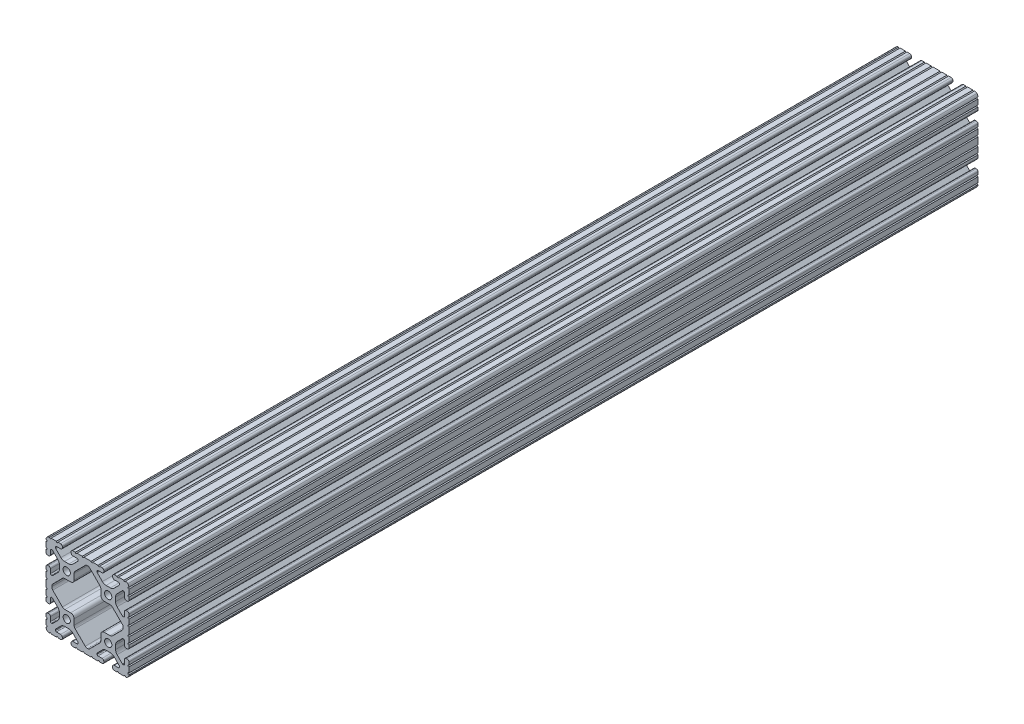
SolidWorks part; units mm, degrees
ref_plane "Front Plane" through (0, 0, 0) normal (0, 0, 1) x (1, 0, 0)
ref_plane "Top Plane" through (0, 0, 0) normal (0, 1, 0) x (1, 0, 0)
ref_plane "Right Plane" through (0, 0, 0) normal (1, 0, 0) x (0, 0, -1)
sketch "Sketch1" plane through (0, 0, 0) normal (0, 0, 1) x (1, 0, 0)
  line L0 (0, 38.1) -> (0, -38.1) construction
  line L1 (-38.1, -38.1) -> (38.1, -38.1) construction
  line L2 (-38.1, -38.1) -> (-38.1, 38.1) construction
  line L3 (-38.1, 38.1) -> (38.1, 38.1) construction
  line L4 (38.1, -38.1) -> (38.1, 38.1) construction
  line L5 (0, 38.1) -> (0, -38.1) construction
  line L6 (-38.1, 0) -> (38.1, 0) construction
  line L7 (-19.05, 19.05) -> (19.05, 19.05) construction
  line L8 (-19.05, 19.05) -> (-19.05, -19.05) construction
  line L9 (-19.05, -19.05) -> (19.05, -19.05) construction
  line L10 (19.05, 19.05) -> (19.05, -19.05) construction
  line L11 (-23.114, 38.1) -> (-23.114, -38.1) construction
  line L12 (-23.114, -38.1) -> (-14.986, 38.1) construction
  line L13 (-14.986, 38.1) -> (-14.986, -38.1) construction
  circle A0 centre (19.05, 19.05) radius 3.3274
  point P0 (0, 0)
  point P9 (0, 0)
  point P12 (-19.05, 0)
  line B0 (-11.3637, -22.8433) -> (-2.0515, -32.1555)
  line B1 (-12.2936, -15.4686) -> (-12.2936, -20.5983)
  line B2 (-20.769, -12.2936) -> (-15.4686, -12.2936)
  line B3 (-31.9021, -2.4756) -> (-23.0141, -11.3637)
  line B4 (-23.0141, 11.3637) -> (-31.9021, 2.4756)
  line B5 (-15.4686, 12.2936) -> (-20.769, 12.2936)
  line B6 (-12.2936, 20.5983) -> (-12.2936, 15.4686)
  line B7 (-2.0515, 32.1555) -> (-11.3637, 22.8433)
  line B8 (11.3637, 22.8433) -> (2.0515, 32.1555)
  line B9 (12.2936, 15.4686) -> (12.2936, 20.5983)
  line B10 (20.769, 12.2936) -> (15.4686, 12.2936)
  line B11 (31.9021, 2.4756) -> (23.0141, 11.3637)
  line B12 (23.0141, -11.3637) -> (31.9021, -2.4756)
  line B13 (15.4686, -12.2936) -> (20.769, -12.2936)
  line B14 (12.2936, -20.5983) -> (12.2936, -15.4686)
  line B15 (2.0515, -32.1555) -> (11.3637, -22.8433)
  line B16 (-4.7773, 38.1) -> (-9.6053, 38.1)
  line B17 (-11.1289, 38.1) -> (-13.4112, 38.1)
  line B18 (-14.986, 36.5252) -> (-14.986, 35.6108)
  line B19 (-13.4112, 34.036) -> (-9.652, 34.036)
  line B20 (-8.763, 33.147) -> (-8.763, 32.4935)
  line B21 (-9.0234, 31.8649) -> (-13.6907, 27.1976)
  line B22 (-17.0493, 25.8064) -> (-21.0507, 25.8064)
  line B23 (-24.4093, 27.1976) -> (-29.1002, 31.8885)
  line B24 (-29.337, 32.7207) -> (-29.337, 33.147)
  line B25 (-28.448, 34.036) -> (-24.6888, 34.036)
  line B26 (-23.114, 35.6108) -> (-23.114, 36.5252)
  line B27 (-24.6888, 38.1) -> (-27.0772, 38.1)
  line B28 (-28.6011, 38.1) -> (-33.4288, 38.1)
  line B29 (-38.1, 33.373) -> (-38.1, 28.5453)
  line B30 (-38.1, 27.0238) -> (-38.1, 24.6302)
  line B31 (-36.5252, 23.0554) -> (-35.6108, 23.0554)
  line B32 (-34.036, 24.6302) -> (-34.036, 28.448)
  line B33 (-33.147, 29.337) -> (-32.6643, 29.337)
  line B34 (-32.0357, 29.0766) -> (-27.1976, 24.2385)
  line B35 (-25.8064, 20.8799) -> (-25.8064, 17.2201)
  line B36 (-27.1976, 13.8615) -> (-31.9489, 9.1101)
  line B37 (-32.7869, 8.763) -> (-33.0603, 8.763)
  line B38 (-34.036, 9.7387) -> (-34.036, 13.4698)
  line B39 (-35.6108, 15.0446) -> (-36.5252, 15.0446)
  line B40 (-38.1, 13.4698) -> (-38.1, 11.075)
  line B41 (-38.1, 9.552) -> (-38.1, 4.7238)
  line B42 (-38.1, 3.2007) -> (-38.1, -3.2007)
  line B43 (-38.1, -4.7238) -> (-38.1, -9.552)
  line B44 (-38.1, -11.075) -> (-38.1, -13.4698)
  line B45 (-36.5252, -15.0446) -> (-35.6108, -15.0446)
  line B46 (-34.036, -13.4698) -> (-34.036, -9.7387)
  line B47 (-33.0603, -8.763) -> (-32.7869, -8.763)
  line B48 (-31.9489, -9.1101) -> (-27.1976, -13.8615)
  line B49 (-25.8064, -17.2201) -> (-25.8064, -20.8799)
  line B50 (-27.1976, -24.2385) -> (-32.0357, -29.0766)
  line B51 (-32.6643, -29.337) -> (-33.147, -29.337)
  line B52 (-34.036, -28.448) -> (-34.036, -24.6302)
  line B53 (-35.6108, -23.0554) -> (-36.5252, -23.0554)
  line B54 (-38.1, -24.6302) -> (-38.1, -27.0238)
  line B55 (-38.1, -28.5453) -> (-38.1, -33.373)
  line B56 (-33.4288, -38.1) -> (-28.6011, -38.1)
  line B57 (-27.0772, -38.1) -> (-24.6888, -38.1)
  line B58 (-23.114, -36.5252) -> (-23.114, -35.6108)
  line B59 (-24.6888, -34.036) -> (-28.448, -34.036)
  line B60 (-29.337, -33.147) -> (-29.337, -32.7207)
  line B61 (-29.1002, -31.8885) -> (-24.4093, -27.1976)
  line B62 (-21.0507, -25.8064) -> (-17.0493, -25.8064)
  line B63 (-13.6907, -27.1976) -> (-9.0234, -31.8649)
  line B64 (-8.763, -32.4935) -> (-8.763, -33.147)
  line B65 (-9.652, -34.036) -> (-13.4112, -34.036)
  line B66 (-14.986, -35.6108) -> (-14.986, -36.5252)
  line B67 (-13.4112, -38.1) -> (-11.1289, -38.1)
  line B68 (-9.6053, -38.1) -> (-4.7773, -38.1)
  line B69 (-3.2537, -38.1) -> (3.2537, -38.1)
  line B70 (4.7773, -38.1) -> (9.6053, -38.1)
  line B71 (11.1289, -38.1) -> (13.4112, -38.1)
  line B72 (14.986, -36.5252) -> (14.986, -35.6108)
  line B73 (13.4112, -34.036) -> (9.652, -34.036)
  line B74 (8.763, -33.147) -> (8.763, -32.4935)
  line B75 (9.0234, -31.8649) -> (13.6907, -27.1976)
  line B76 (17.0493, -25.8064) -> (21.0507, -25.8064)
  line B77 (24.4093, -27.1976) -> (29.1002, -31.8885)
  line B78 (29.337, -32.7207) -> (29.337, -33.147)
  line B79 (28.448, -34.036) -> (24.6888, -34.036)
  line B80 (23.114, -35.6108) -> (23.114, -36.5252)
  line B81 (24.6888, -38.1) -> (27.0772, -38.1)
  line B82 (28.6011, -38.1) -> (33.4288, -38.1)
  line B83 (38.1, -33.373) -> (38.1, -28.5453)
  line B84 (38.1, -27.0238) -> (38.1, -24.6302)
  line B85 (36.5252, -23.0554) -> (35.6108, -23.0554)
  line B86 (34.036, -24.6302) -> (34.036, -28.448)
  line B87 (33.147, -29.337) -> (32.6643, -29.337)
  line B88 (32.0357, -29.0766) -> (27.1976, -24.2385)
  line B89 (25.8064, -20.8799) -> (25.8064, -17.2201)
  line B90 (27.1976, -13.8615) -> (31.9489, -9.1101)
  line B91 (32.7869, -8.763) -> (33.0603, -8.763)
  line B92 (34.036, -9.7387) -> (34.036, -13.4698)
  line B93 (35.6108, -15.0446) -> (36.5252, -15.0446)
  line B94 (38.1, -13.4698) -> (38.1, -11.075)
  line B95 (38.1, -9.552) -> (38.1, -4.7238)
  line B96 (38.1, -3.2007) -> (38.1, 3.2007)
  line B97 (38.1, 4.7238) -> (38.1, 9.552)
  line B98 (38.1, 11.075) -> (38.1, 13.4698)
  line B99 (36.5252, 15.0446) -> (35.6108, 15.0446)
  line B100 (34.036, 13.4698) -> (34.036, 9.7387)
  line B101 (33.0603, 8.763) -> (32.7869, 8.763)
  line B102 (31.9489, 9.1101) -> (27.1976, 13.8615)
  line B103 (25.8064, 17.2201) -> (25.8064, 20.8799)
  line B104 (27.1976, 24.2385) -> (32.0357, 29.0766)
  line B105 (32.6643, 29.337) -> (33.147, 29.337)
  line B106 (34.036, 28.448) -> (34.036, 24.6302)
  line B107 (35.6108, 23.0554) -> (36.5252, 23.0554)
  line B108 (38.1, 24.6302) -> (38.1, 27.0238)
  line B109 (38.1, 28.5453) -> (38.1, 33.373)
  line B110 (33.4288, 38.1) -> (28.6011, 38.1)
  line B111 (27.0772, 38.1) -> (24.6888, 38.1)
  line B112 (23.114, 36.5252) -> (23.114, 35.6108)
  line B113 (24.6888, 34.036) -> (28.448, 34.036)
  line B114 (29.337, 33.147) -> (29.337, 32.7207)
  line B115 (29.1002, 31.8885) -> (24.4093, 27.1976)
  line B116 (21.0507, 25.8064) -> (17.0493, 25.8064)
  line B117 (13.6907, 27.1976) -> (9.0234, 31.8649)
  line B118 (8.763, 32.4935) -> (8.763, 33.147)
  line B119 (9.652, 34.036) -> (13.4112, 34.036)
  line B120 (14.986, 35.6108) -> (14.986, 36.5252)
  line B121 (13.4112, 38.1) -> (11.1289, 38.1)
  line B122 (9.6053, 38.1) -> (4.7773, 38.1)
  line B123 (3.2537, 38.1) -> (-3.2537, 38.1)
  circle B124 centre (-19.05, 19.05) radius 3.3274
  circle B125 centre (-19.05, -19.05) radius 3.3274
  circle B126 centre (19.05, -19.05) radius 3.3274
  circle B127 centre (19.05, 19.05) radius 3.3274
  arc B128 (0, -33.011) -> (2.0515, -32.1555) centre (-0.0139, -30.09) ccw
  arc B129 (-2.0515, -32.1555) -> (0, -33.011) centre (0.0139, -30.09) ccw
  arc B130 (-12.2936, -20.5983) -> (-11.3637, -22.8433) centre (-9.1186, -20.5983) ccw
  arc B131 (-12.2936, -15.4686) -> (-15.4686, -12.2936) centre (-15.4686, -15.4686) ccw
  arc B132 (-23.0141, -11.3637) -> (-20.769, -12.2936) centre (-20.769, -9.1186) ccw
  arc B133 (-32.7287, 0) -> (-31.9021, -2.4756) centre (-29.8367, -0.4102) ccw
  arc B134 (-31.9021, 2.4756) -> (-32.7287, 0) centre (-29.8367, 0.4102) ccw
  arc B135 (-20.769, 12.2936) -> (-23.0141, 11.3637) centre (-20.769, 9.1186) ccw
  arc B136 (-15.4686, 12.2936) -> (-12.2936, 15.4686) centre (-15.4686, 15.4686) ccw
  arc B137 (-11.3637, 22.8433) -> (-12.2936, 20.5983) centre (-9.1186, 20.5983) ccw
  arc B138 (0, 33.011) -> (-2.0515, 32.1555) centre (0.0139, 30.09) ccw
  arc B139 (2.0515, 32.1555) -> (0, 33.011) centre (-0.0139, 30.09) ccw
  arc B140 (12.2936, 20.5983) -> (11.3637, 22.8433) centre (9.1186, 20.5983) ccw
  arc B141 (12.2936, 15.4686) -> (15.4686, 12.2936) centre (15.4686, 15.4686) ccw
  arc B142 (23.0141, 11.3637) -> (20.769, 12.2936) centre (20.769, 9.1186) ccw
  arc B143 (32.7287, 0) -> (31.9021, 2.4756) centre (29.8367, 0.4102) ccw
  arc B144 (31.9021, -2.4756) -> (32.7287, 0) centre (29.8367, -0.4102) ccw
  arc B145 (20.769, -12.2936) -> (23.0141, -11.3637) centre (20.769, -9.1186) ccw
  arc B146 (15.4686, -12.2936) -> (12.2936, -15.4686) centre (15.4686, -15.4686) ccw
  arc B147 (11.3637, -22.8433) -> (12.2936, -20.5983) centre (9.1186, -20.5983) ccw
  arc B148 (-4.7773, 38.1) -> (-3.2537, 38.1) centre (-4.0155, 38.0824) ccw
  arc B149 (-11.1289, 38.1) -> (-9.6053, 38.1) centre (-10.3671, 38.0824) ccw
  arc B150 (-13.4112, 38.1) -> (-14.986, 36.5252) centre (-13.4112, 36.5252) ccw
  arc B151 (-14.986, 35.6108) -> (-13.4112, 34.036) centre (-13.4112, 35.6108) ccw
  arc B152 (-8.763, 33.147) -> (-9.652, 34.036) centre (-9.652, 33.147) ccw
  arc B153 (-9.0234, 31.8649) -> (-8.763, 32.4935) centre (-9.652, 32.4935) ccw
  arc B154 (-17.0493, 25.8064) -> (-13.6907, 27.1976) centre (-17.0493, 30.5562) ccw
  arc B155 (-24.4093, 27.1976) -> (-21.0507, 25.8064) centre (-21.0507, 30.5562) ccw
  arc B156 (-29.337, 32.7207) -> (-29.1002, 31.8885) centre (-28.4716, 32.5172) ccw
  arc B157 (-28.448, 34.036) -> (-29.337, 33.147) centre (-28.448, 33.147) ccw
  arc B158 (-24.6888, 34.036) -> (-23.114, 35.6108) centre (-24.6888, 35.6108) ccw
  arc B159 (-23.114, 36.5252) -> (-24.6888, 38.1) centre (-24.6888, 36.5252) ccw
  arc B160 (-28.6011, 38.1) -> (-27.0772, 38.1) centre (-27.8392, 38.0824) ccw
  arc B161 (-34.9527, 38.1) -> (-33.4288, 38.1) centre (-34.1907, 38.0824) ccw
  arc B162 (-34.9527, 38.1) -> (-37.0861, 37.1826) centre (-34.8521, 34.9266) ccw
  arc B163 (-37.0861, 37.1826) -> (-38.1, 34.8455) centre (-34.925, 34.8566) ccw
  arc B164 (-38.1, 33.373) -> (-38.1, 34.8455) centre (-37.9035, 34.1092) ccw
  arc B165 (-38.1, 27.0238) -> (-38.1, 28.5453) centre (-37.9035, 27.7845) ccw
  arc B166 (-38.1, 24.6302) -> (-36.5252, 23.0554) centre (-36.5252, 24.6302) ccw
  arc B167 (-35.6108, 23.0554) -> (-34.036, 24.6302) centre (-35.6108, 24.6302) ccw
  arc B168 (-33.147, 29.337) -> (-34.036, 28.448) centre (-33.147, 28.448) ccw
  arc B169 (-32.0357, 29.0766) -> (-32.6643, 29.337) centre (-32.6643, 28.448) ccw
  arc B170 (-25.8064, 20.8799) -> (-27.1976, 24.2385) centre (-30.5562, 20.8799) ccw
  arc B171 (-27.1976, 13.8615) -> (-25.8064, 17.2201) centre (-30.5562, 17.2201) ccw
  arc B172 (-32.7869, 8.763) -> (-31.9489, 9.1101) centre (-32.7869, 9.9481) ccw
  arc B173 (-34.036, 9.7387) -> (-33.0603, 8.763) centre (-33.0603, 9.7387) ccw
  arc B174 (-34.036, 13.4698) -> (-35.6108, 15.0446) centre (-35.6108, 13.4698) ccw
  arc B175 (-36.5252, 15.0446) -> (-38.1, 13.4698) centre (-36.5252, 13.4698) ccw
  arc B176 (-38.1, 9.552) -> (-38.1, 11.075) centre (-37.9035, 10.3135) ccw
  arc B177 (-38.1, 3.2007) -> (-38.1, 4.7238) centre (-37.9035, 3.9622) ccw
  arc B178 (-38.1, -4.7238) -> (-38.1, -3.2007) centre (-37.9035, -3.9622) ccw
  arc B179 (-38.1, -11.075) -> (-38.1, -9.552) centre (-37.9035, -10.3135) ccw
  arc B180 (-38.1, -13.4698) -> (-36.5252, -15.0446) centre (-36.5252, -13.4698) ccw
  arc B181 (-35.6108, -15.0446) -> (-34.036, -13.4698) centre (-35.6108, -13.4698) ccw
  arc B182 (-33.0603, -8.763) -> (-34.036, -9.7387) centre (-33.0603, -9.7387) ccw
  arc B183 (-31.9489, -9.1101) -> (-32.7869, -8.763) centre (-32.7869, -9.9481) ccw
  arc B184 (-25.8064, -17.2201) -> (-27.1976, -13.8615) centre (-30.5562, -17.2201) ccw
  arc B185 (-27.1976, -24.2385) -> (-25.8064, -20.8799) centre (-30.5562, -20.8799) ccw
  arc B186 (-32.6643, -29.337) -> (-32.0357, -29.0766) centre (-32.6643, -28.448) ccw
  arc B187 (-34.036, -28.448) -> (-33.147, -29.337) centre (-33.147, -28.448) ccw
  arc B188 (-34.036, -24.6302) -> (-35.6108, -23.0554) centre (-35.6108, -24.6302) ccw
  arc B189 (-36.5252, -23.0554) -> (-38.1, -24.6302) centre (-36.5252, -24.6302) ccw
  arc B190 (-38.1, -28.5453) -> (-38.1, -27.0238) centre (-37.9035, -27.7845) ccw
  arc B191 (-38.1, -34.8455) -> (-38.1, -33.373) centre (-37.9035, -34.1092) ccw
  arc B192 (-38.1, -34.8455) -> (-37.0861, -37.1826) centre (-34.925, -34.8566) ccw
  arc B193 (-37.0861, -37.1826) -> (-34.9527, -38.1) centre (-34.8521, -34.9266) ccw
  arc B194 (-33.4288, -38.1) -> (-34.9527, -38.1) centre (-34.1907, -38.0824) ccw
  arc B195 (-27.0772, -38.1) -> (-28.6011, -38.1) centre (-27.8392, -38.0824) ccw
  arc B196 (-24.6888, -38.1) -> (-23.114, -36.5252) centre (-24.6888, -36.5252) ccw
  arc B197 (-23.114, -35.6108) -> (-24.6888, -34.036) centre (-24.6888, -35.6108) ccw
  arc B198 (-29.337, -33.147) -> (-28.448, -34.036) centre (-28.448, -33.147) ccw
  arc B199 (-29.1002, -31.8885) -> (-29.337, -32.7207) centre (-28.4716, -32.5172) ccw
  arc B200 (-21.0507, -25.8064) -> (-24.4093, -27.1976) centre (-21.0507, -30.5562) ccw
  arc B201 (-13.6907, -27.1976) -> (-17.0493, -25.8064) centre (-17.0493, -30.5562) ccw
  arc B202 (-8.763, -32.4935) -> (-9.0234, -31.8649) centre (-9.652, -32.4935) ccw
  arc B203 (-9.652, -34.036) -> (-8.763, -33.147) centre (-9.652, -33.147) ccw
  arc B204 (-13.4112, -34.036) -> (-14.986, -35.6108) centre (-13.4112, -35.6108) ccw
  arc B205 (-14.986, -36.5252) -> (-13.4112, -38.1) centre (-13.4112, -36.5252) ccw
  arc B206 (-9.6053, -38.1) -> (-11.1289, -38.1) centre (-10.3671, -38.0824) ccw
  arc B207 (-3.2537, -38.1) -> (-4.7773, -38.1) centre (-4.0155, -38.0824) ccw
  arc B208 (4.7773, -38.1) -> (3.2537, -38.1) centre (4.0155, -38.0824) ccw
  arc B209 (11.1289, -38.1) -> (9.6053, -38.1) centre (10.3671, -38.0824) ccw
  arc B210 (13.4112, -38.1) -> (14.986, -36.5252) centre (13.4112, -36.5252) ccw
  arc B211 (14.986, -35.6108) -> (13.4112, -34.036) centre (13.4112, -35.6108) ccw
  arc B212 (8.763, -33.147) -> (9.652, -34.036) centre (9.652, -33.147) ccw
  arc B213 (9.0234, -31.8649) -> (8.763, -32.4935) centre (9.652, -32.4935) ccw
  arc B214 (17.0493, -25.8064) -> (13.6907, -27.1976) centre (17.0493, -30.5562) ccw
  arc B215 (24.4093, -27.1976) -> (21.0507, -25.8064) centre (21.0507, -30.5562) ccw
  arc B216 (29.337, -32.7207) -> (29.1002, -31.8885) centre (28.4716, -32.5172) ccw
  arc B217 (28.448, -34.036) -> (29.337, -33.147) centre (28.448, -33.147) ccw
  arc B218 (24.6888, -34.036) -> (23.114, -35.6108) centre (24.6888, -35.6108) ccw
  arc B219 (23.114, -36.5252) -> (24.6888, -38.1) centre (24.6888, -36.5252) ccw
  arc B220 (28.6011, -38.1) -> (27.0772, -38.1) centre (27.8392, -38.0824) ccw
  arc B221 (34.9527, -38.1) -> (33.4288, -38.1) centre (34.1907, -38.0824) ccw
  arc B222 (34.9527, -38.1) -> (37.0861, -37.1826) centre (34.8521, -34.9266) ccw
  arc B223 (37.0861, -37.1826) -> (38.1, -34.8455) centre (34.925, -34.8566) ccw
  arc B224 (38.1, -33.373) -> (38.1, -34.8455) centre (37.9035, -34.1092) ccw
  arc B225 (38.1, -27.0238) -> (38.1, -28.5453) centre (37.9035, -27.7845) ccw
  arc B226 (38.1, -24.6302) -> (36.5252, -23.0554) centre (36.5252, -24.6302) ccw
  arc B227 (35.6108, -23.0554) -> (34.036, -24.6302) centre (35.6108, -24.6302) ccw
  arc B228 (33.147, -29.337) -> (34.036, -28.448) centre (33.147, -28.448) ccw
  arc B229 (32.0357, -29.0766) -> (32.6643, -29.337) centre (32.6643, -28.448) ccw
  arc B230 (25.8064, -20.8799) -> (27.1976, -24.2385) centre (30.5562, -20.8799) ccw
  arc B231 (27.1976, -13.8615) -> (25.8064, -17.2201) centre (30.5562, -17.2201) ccw
  arc B232 (32.7869, -8.763) -> (31.9489, -9.1101) centre (32.7869, -9.9481) ccw
  arc B233 (34.036, -9.7387) -> (33.0603, -8.763) centre (33.0603, -9.7387) ccw
  arc B234 (34.036, -13.4698) -> (35.6108, -15.0446) centre (35.6108, -13.4698) ccw
  arc B235 (36.5252, -15.0446) -> (38.1, -13.4698) centre (36.5252, -13.4698) ccw
  arc B236 (38.1, -9.552) -> (38.1, -11.075) centre (37.9035, -10.3135) ccw
  arc B237 (38.1, -3.2007) -> (38.1, -4.7238) centre (37.9035, -3.9622) ccw
  arc B238 (38.1, 4.7238) -> (38.1, 3.2007) centre (37.9035, 3.9622) ccw
  arc B239 (38.1, 11.075) -> (38.1, 9.552) centre (37.9035, 10.3135) ccw
  arc B240 (38.1, 13.4698) -> (36.5252, 15.0446) centre (36.5252, 13.4698) ccw
  arc B241 (35.6108, 15.0446) -> (34.036, 13.4698) centre (35.6108, 13.4698) ccw
  arc B242 (33.0603, 8.763) -> (34.036, 9.7387) centre (33.0603, 9.7387) ccw
  arc B243 (31.9489, 9.1101) -> (32.7869, 8.763) centre (32.7869, 9.9481) ccw
  arc B244 (25.8064, 17.2201) -> (27.1976, 13.8615) centre (30.5562, 17.2201) ccw
  arc B245 (27.1976, 24.2385) -> (25.8064, 20.8799) centre (30.5562, 20.8799) ccw
  arc B246 (32.6643, 29.337) -> (32.0357, 29.0766) centre (32.6643, 28.448) ccw
  arc B247 (34.036, 28.448) -> (33.147, 29.337) centre (33.147, 28.448) ccw
  arc B248 (34.036, 24.6302) -> (35.6108, 23.0554) centre (35.6108, 24.6302) ccw
  arc B249 (36.5252, 23.0554) -> (38.1, 24.6302) centre (36.5252, 24.6302) ccw
  arc B250 (38.1, 28.5453) -> (38.1, 27.0238) centre (37.9035, 27.7845) ccw
  arc B251 (38.1, 34.8455) -> (38.1, 33.373) centre (37.9035, 34.1092) ccw
  arc B252 (38.1, 34.8455) -> (37.0861, 37.1826) centre (34.925, 34.8566) ccw
  arc B253 (37.0861, 37.1826) -> (34.9527, 38.1) centre (34.8521, 34.9266) ccw
  arc B254 (33.4288, 38.1) -> (34.9527, 38.1) centre (34.1907, 38.0824) ccw
  arc B255 (27.0772, 38.1) -> (28.6011, 38.1) centre (27.8392, 38.0824) ccw
  arc B256 (24.6888, 38.1) -> (23.114, 36.5252) centre (24.6888, 36.5252) ccw
  arc B257 (23.114, 35.6108) -> (24.6888, 34.036) centre (24.6888, 35.6108) ccw
  arc B258 (29.337, 33.147) -> (28.448, 34.036) centre (28.448, 33.147) ccw
  arc B259 (29.1002, 31.8885) -> (29.337, 32.7207) centre (28.4716, 32.5172) ccw
  arc B260 (21.0507, 25.8064) -> (24.4093, 27.1976) centre (21.0507, 30.5562) ccw
  arc B261 (13.6907, 27.1976) -> (17.0493, 25.8064) centre (17.0493, 30.5562) ccw
  arc B262 (8.763, 32.4935) -> (9.0234, 31.8649) centre (9.652, 32.4935) ccw
  arc B263 (9.652, 34.036) -> (8.763, 33.147) centre (9.652, 33.147) ccw
  arc B264 (13.4112, 34.036) -> (14.986, 35.6108) centre (13.4112, 35.6108) ccw
  arc B265 (14.986, 36.5252) -> (13.4112, 38.1) centre (13.4112, 36.5252) ccw
  arc B266 (9.6053, 38.1) -> (11.1289, 38.1) centre (10.3671, 38.0824) ccw
  arc B267 (3.2537, 38.1) -> (4.7773, 38.1) centre (4.0155, 38.0824) ccw
  dimension "Center Hole Diameter" = 6.6548
  dimension "Rail Width" = 76.2
  dimension "Rail Height" = 76.2
  dimension "T-Slot Width" = 8.128
sketch_block_instance "Block1-1"
sketch_block "Block1"
sketch "Sketch2" plane through (0, 0, 0) normal (1, 0, 0) x (0, 0, -1)
  line L0 (-390, 0) -> (390, 0) construction
  line L1 (-390, 38.1) -> (-390, -38.1) construction
  line L2 (-390, -38.1) -> (390, -38.1) construction
  line L3 (390, -38.1) -> (390, 38.1) construction
  line L4 (-288.4, 0) -> (-288.4, 38.1) construction
  line L5 (-288.4, 38.1) -> (288.4, 38.1) construction
  line L6 (288.4, 38.1) -> (288.4, 0) construction
  point P5 (288.4, 0)
  point P10 (-288.4, 0)
  dimension "D1" = 101.6
  dimension "Length" = 780
  dimension "D2" = 101.6
sketch "Sketch3" plane through (0, 0, 0) normal (0, 0, 1) x (1, 0, 0)
  line L0 (-11.3637, -22.8433) -> (-2.0515, -32.1555) construction
  line L1 (-12.2936, -15.4686) -> (-12.2936, -20.5983) construction
  line L2 (-20.769, -12.2936) -> (-15.4686, -12.2936) construction
  line L3 (-31.9021, -2.4756) -> (-23.0141, -11.3637) construction
  line L4 (-23.0141, 11.3637) -> (-31.9021, 2.4756) construction
  line L5 (-15.4686, 12.2936) -> (-20.769, 12.2936) construction
  line L6 (-12.2936, 20.5983) -> (-12.2936, 15.4686) construction
  line L7 (-2.0515, 32.1555) -> (-11.3637, 22.8433) construction
  line L8 (11.3637, 22.8433) -> (2.0515, 32.1555) construction
  line L9 (12.2936, 15.4686) -> (12.2936, 20.5983) construction
  line L10 (20.769, 12.2936) -> (15.4686, 12.2936) construction
  line L11 (31.9021, 2.4756) -> (23.0141, 11.3637) construction
  line L12 (23.0141, -11.3637) -> (31.9021, -2.4756) construction
  line L13 (15.4686, -12.2936) -> (20.769, -12.2936) construction
  line L14 (12.2936, -20.5983) -> (12.2936, -15.4686) construction
  line L15 (2.0515, -32.1555) -> (11.3637, -22.8433) construction
  line L16 (34.036, 28.448) -> (34.036, 24.6302) construction
  line L17 (35.6108, 23.0554) -> (36.5252, 23.0554) construction
  line L18 (38.1, 24.6302) -> (38.1, 27.0238) construction
  line L19 (38.1, 28.5453) -> (38.1, 33.373) construction
  line L20 (33.4288, 38.1) -> (28.6011, 38.1) construction
  line L21 (27.0772, 38.1) -> (24.6888, 38.1) construction
  line L22 (23.114, 36.5252) -> (23.114, 35.6108) construction
  line L23 (24.6888, 34.036) -> (28.448, 34.036) construction
  line L24 (29.337, 33.147) -> (29.337, 32.7207) construction
  line L25 (29.1002, 31.8885) -> (24.4093, 27.1976) construction
  line L26 (21.0507, 25.8064) -> (17.0493, 25.8064) construction
  line L27 (13.6907, 27.1976) -> (9.0234, 31.8649) construction
  line L28 (8.763, 32.4935) -> (8.763, 33.147) construction
  line L29 (9.652, 34.036) -> (13.4112, 34.036) construction
  line L30 (14.986, 35.6108) -> (14.986, 36.5252) construction
  line L31 (13.4112, 38.1) -> (11.1289, 38.1) construction
  line L32 (9.6053, 38.1) -> (4.7773, 38.1) construction
  line L33 (3.2537, 38.1) -> (-3.2537, 38.1) construction
  line L34 (-4.7773, 38.1) -> (-9.6053, 38.1) construction
  line L35 (-11.1289, 38.1) -> (-13.4112, 38.1) construction
  line L36 (-14.986, 36.5252) -> (-14.986, 35.6108) construction
  line L37 (-13.4112, 34.036) -> (-9.652, 34.036) construction
  line L38 (-8.763, 33.147) -> (-8.763, 32.4935) construction
  line L39 (-9.0234, 31.8649) -> (-13.6907, 27.1976) construction
  line L40 (-17.0493, 25.8064) -> (-21.0507, 25.8064) construction
  line L41 (-24.4093, 27.1976) -> (-29.1002, 31.8885) construction
  line L42 (-29.337, 32.7207) -> (-29.337, 33.147) construction
  line L43 (-28.448, 34.036) -> (-24.6888, 34.036) construction
  line L44 (-23.114, 35.6108) -> (-23.114, 36.5252) construction
  line L45 (-24.6888, 38.1) -> (-27.0772, 38.1) construction
  line L46 (-28.6011, 38.1) -> (-33.4288, 38.1) construction
  line L47 (-38.1, 33.373) -> (-38.1, 28.5453) construction
  line L48 (-38.1, 27.0238) -> (-38.1, 24.6302) construction
  line L49 (-36.5252, 23.0554) -> (-35.6108, 23.0554) construction
  line L50 (-34.036, 24.6302) -> (-34.036, 28.448) construction
  line L51 (-33.147, 29.337) -> (-32.6643, 29.337) construction
  line L52 (-32.0357, 29.0766) -> (-27.1976, 24.2385) construction
  line L53 (-25.8064, 20.8799) -> (-25.8064, 17.2201) construction
  line L54 (-27.1976, 13.8615) -> (-31.9489, 9.1101) construction
  line L55 (-32.7869, 8.763) -> (-33.0603, 8.763) construction
  line L56 (-34.036, 9.7387) -> (-34.036, 13.4698) construction
  line L57 (-35.6108, 15.0446) -> (-36.5252, 15.0446) construction
  line L58 (-38.1, 13.4698) -> (-38.1, 11.075) construction
  line L59 (-38.1, 9.552) -> (-38.1, 4.7238) construction
  line L60 (-38.1, 3.2007) -> (-38.1, -3.2007) construction
  line L61 (-38.1, -4.7238) -> (-38.1, -9.552) construction
  line L62 (-38.1, -11.075) -> (-38.1, -13.4698) construction
  line L63 (-36.5252, -15.0446) -> (-35.6108, -15.0446) construction
  line L64 (-34.036, -13.4698) -> (-34.036, -9.7387) construction
  line L65 (-33.0603, -8.763) -> (-32.7869, -8.763) construction
  line L66 (-31.9489, -9.1101) -> (-27.1976, -13.8615) construction
  line L67 (-25.8064, -17.2201) -> (-25.8064, -20.8799) construction
  line L68 (-27.1976, -24.2385) -> (-32.0357, -29.0766) construction
  line L69 (-32.6643, -29.337) -> (-33.147, -29.337) construction
  line L70 (-34.036, -28.448) -> (-34.036, -24.6302) construction
  line L71 (-35.6108, -23.0554) -> (-36.5252, -23.0554) construction
  line L72 (-38.1, -24.6302) -> (-38.1, -27.0238) construction
  line L73 (-38.1, -28.5453) -> (-38.1, -33.373) construction
  line L74 (-33.4288, -38.1) -> (-28.6011, -38.1) construction
  line L75 (-27.0772, -38.1) -> (-24.6888, -38.1) construction
  line L76 (-23.114, -36.5252) -> (-23.114, -35.6108) construction
  line L77 (-24.6888, -34.036) -> (-28.448, -34.036) construction
  line L78 (-29.337, -33.147) -> (-29.337, -32.7207) construction
  line L79 (-29.1002, -31.8885) -> (-24.4093, -27.1976) construction
  line L80 (-21.0507, -25.8064) -> (-17.0493, -25.8064) construction
  line L81 (-13.6907, -27.1976) -> (-9.0234, -31.8649) construction
  line L82 (-8.763, -32.4935) -> (-8.763, -33.147) construction
  line L83 (-9.652, -34.036) -> (-13.4112, -34.036) construction
  line L84 (-14.986, -35.6108) -> (-14.986, -36.5252) construction
  line L85 (-13.4112, -38.1) -> (-11.1289, -38.1) construction
  line L86 (-9.6053, -38.1) -> (-4.7773, -38.1) construction
  line L87 (-3.2537, -38.1) -> (3.2537, -38.1) construction
  line L88 (4.7773, -38.1) -> (9.6053, -38.1) construction
  line L89 (11.1289, -38.1) -> (13.4112, -38.1) construction
  line L90 (14.986, -36.5252) -> (14.986, -35.6108) construction
  line L91 (13.4112, -34.036) -> (9.652, -34.036) construction
  line L92 (8.763, -33.147) -> (8.763, -32.4935) construction
  line L93 (9.0234, -31.8649) -> (13.6907, -27.1976) construction
  line L94 (17.0493, -25.8064) -> (21.0507, -25.8064) construction
  line L95 (24.4093, -27.1976) -> (29.1002, -31.8885) construction
  line L96 (29.337, -32.7207) -> (29.337, -33.147) construction
  line L97 (28.448, -34.036) -> (24.6888, -34.036) construction
  line L98 (23.114, -35.6108) -> (23.114, -36.5252) construction
  line L99 (24.6888, -38.1) -> (27.0772, -38.1) construction
  line L100 (28.6011, -38.1) -> (33.4288, -38.1) construction
  line L101 (38.1, -33.373) -> (38.1, -28.5453) construction
  line L102 (38.1, -27.0238) -> (38.1, -24.6302) construction
  line L103 (36.5252, -23.0554) -> (35.6108, -23.0554) construction
  line L104 (34.036, -24.6302) -> (34.036, -28.448) construction
  line L105 (33.147, -29.337) -> (32.6643, -29.337) construction
  line L106 (32.0357, -29.0766) -> (27.1976, -24.2385) construction
  line L107 (25.8064, -20.8799) -> (25.8064, -17.2201) construction
  line L108 (27.1976, -13.8615) -> (31.9489, -9.1101) construction
  line L109 (32.7869, -8.763) -> (33.0603, -8.763) construction
  line L110 (34.036, -9.7387) -> (34.036, -13.4698) construction
  line L111 (35.6108, -15.0446) -> (36.5252, -15.0446) construction
  line L112 (38.1, -13.4698) -> (38.1, -11.075) construction
  line L113 (38.1, -9.552) -> (38.1, -4.7238) construction
  line L114 (38.1, -3.2007) -> (38.1, 3.2007) construction
  line L115 (38.1, 4.7238) -> (38.1, 9.552) construction
  line L116 (38.1, 11.075) -> (38.1, 13.4698) construction
  line L117 (36.5252, 15.0446) -> (35.6108, 15.0446) construction
  line L118 (34.036, 13.4698) -> (34.036, 9.7387) construction
  line L119 (33.0603, 8.763) -> (32.7869, 8.763) construction
  line L120 (31.9489, 9.1101) -> (27.1976, 13.8615) construction
  line L121 (25.8064, 17.2201) -> (25.8064, 20.8799) construction
  line L122 (27.1976, 24.2385) -> (32.0357, 29.0766) construction
  line L123 (32.6643, 29.337) -> (33.147, 29.337) construction
  line L124 (-11.3637, -22.8433) -> (-2.0515, -32.1555)
  line L125 (-12.2936, -15.4686) -> (-12.2936, -20.5983)
  line L126 (-20.769, -12.2936) -> (-15.4686, -12.2936)
  line L127 (-31.9021, -2.4756) -> (-23.0141, -11.3637)
  line L128 (-23.0141, 11.3637) -> (-31.9021, 2.4756)
  line L129 (-15.4686, 12.2936) -> (-20.769, 12.2936)
  line L130 (-12.2936, 20.5983) -> (-12.2936, 15.4686)
  line L131 (-2.0515, 32.1555) -> (-11.3637, 22.8433)
  line L132 (11.3637, 22.8433) -> (2.0515, 32.1555)
  line L133 (12.2936, 15.4686) -> (12.2936, 20.5983)
  line L134 (20.769, 12.2936) -> (15.4686, 12.2936)
  line L135 (31.9021, 2.4756) -> (23.0141, 11.3637)
  line L136 (23.0141, -11.3637) -> (31.9021, -2.4756)
  line L137 (15.4686, -12.2936) -> (20.769, -12.2936)
  line L138 (12.2936, -20.5983) -> (12.2936, -15.4686)
  line L139 (2.0515, -32.1555) -> (11.3637, -22.8433)
  line L140 (34.036, 28.448) -> (34.036, 24.6302)
  line L141 (35.6108, 23.0554) -> (36.5252, 23.0554)
  line L142 (38.1, 24.6302) -> (38.1, 27.0238)
  line L143 (38.1, 28.5453) -> (38.1, 33.373)
  line L144 (33.4288, 38.1) -> (28.6011, 38.1)
  line L145 (27.0772, 38.1) -> (24.6888, 38.1)
  line L146 (23.114, 36.5252) -> (23.114, 35.6108)
  line L147 (24.6888, 34.036) -> (28.448, 34.036)
  line L148 (29.337, 33.147) -> (29.337, 32.7207)
  line L149 (29.1002, 31.8885) -> (24.4093, 27.1976)
  line L150 (21.0507, 25.8064) -> (17.0493, 25.8064)
  line L151 (13.6907, 27.1976) -> (9.0234, 31.8649)
  line L152 (8.763, 32.4935) -> (8.763, 33.147)
  line L153 (9.652, 34.036) -> (13.4112, 34.036)
  line L154 (14.986, 35.6108) -> (14.986, 36.5252)
  line L155 (13.4112, 38.1) -> (11.1289, 38.1)
  line L156 (9.6053, 38.1) -> (4.7773, 38.1)
  line L157 (3.2537, 38.1) -> (-3.2537, 38.1)
  line L158 (-4.7773, 38.1) -> (-9.6053, 38.1)
  line L159 (-11.1289, 38.1) -> (-13.4112, 38.1)
  line L160 (-14.986, 36.5252) -> (-14.986, 35.6108)
  line L161 (-13.4112, 34.036) -> (-9.652, 34.036)
  line L162 (-8.763, 33.147) -> (-8.763, 32.4935)
  line L163 (-9.0234, 31.8649) -> (-13.6907, 27.1976)
  line L164 (-17.0493, 25.8064) -> (-21.0507, 25.8064)
  line L165 (-24.4093, 27.1976) -> (-29.1002, 31.8885)
  line L166 (-29.337, 32.7207) -> (-29.337, 33.147)
  line L167 (-28.448, 34.036) -> (-24.6888, 34.036)
  line L168 (-23.114, 35.6108) -> (-23.114, 36.5252)
  line L169 (-24.6888, 38.1) -> (-27.0772, 38.1)
  line L170 (-28.6011, 38.1) -> (-33.4288, 38.1)
  line L171 (-38.1, 33.373) -> (-38.1, 28.5453)
  line L172 (-38.1, 27.0238) -> (-38.1, 24.6302)
  line L173 (-36.5252, 23.0554) -> (-35.6108, 23.0554)
  line L174 (-34.036, 24.6302) -> (-34.036, 28.448)
  line L175 (-33.147, 29.337) -> (-32.6643, 29.337)
  line L176 (-32.0357, 29.0766) -> (-27.1976, 24.2385)
  line L177 (-25.8064, 20.8799) -> (-25.8064, 17.2201)
  line L178 (-27.1976, 13.8615) -> (-31.9489, 9.1101)
  line L179 (-32.7869, 8.763) -> (-33.0603, 8.763)
  line L180 (-34.036, 9.7387) -> (-34.036, 13.4698)
  line L181 (-35.6108, 15.0446) -> (-36.5252, 15.0446)
  line L182 (-38.1, 13.4698) -> (-38.1, 11.075)
  line L183 (-38.1, 9.552) -> (-38.1, 4.7238)
  line L184 (-38.1, 3.2007) -> (-38.1, -3.2007)
  line L185 (-38.1, -4.7238) -> (-38.1, -9.552)
  line L186 (-38.1, -11.075) -> (-38.1, -13.4698)
  line L187 (-36.5252, -15.0446) -> (-35.6108, -15.0446)
  line L188 (-34.036, -13.4698) -> (-34.036, -9.7387)
  line L189 (-33.0603, -8.763) -> (-32.7869, -8.763)
  line L190 (-31.9489, -9.1101) -> (-27.1976, -13.8615)
  line L191 (-25.8064, -17.2201) -> (-25.8064, -20.8799)
  line L192 (-27.1976, -24.2385) -> (-32.0357, -29.0766)
  line L193 (-32.6643, -29.337) -> (-33.147, -29.337)
  line L194 (-34.036, -28.448) -> (-34.036, -24.6302)
  line L195 (-35.6108, -23.0554) -> (-36.5252, -23.0554)
  line L196 (-38.1, -24.6302) -> (-38.1, -27.0238)
  line L197 (-38.1, -28.5453) -> (-38.1, -33.373)
  line L198 (-33.4288, -38.1) -> (-28.6011, -38.1)
  line L199 (-27.0772, -38.1) -> (-24.6888, -38.1)
  line L200 (-23.114, -36.5252) -> (-23.114, -35.6108)
  line L201 (-24.6888, -34.036) -> (-28.448, -34.036)
  line L202 (-29.337, -33.147) -> (-29.337, -32.7207)
  line L203 (-29.1002, -31.8885) -> (-24.4093, -27.1976)
  line L204 (-21.0507, -25.8064) -> (-17.0493, -25.8064)
  line L205 (-13.6907, -27.1976) -> (-9.0234, -31.8649)
  line L206 (-8.763, -32.4935) -> (-8.763, -33.147)
  line L207 (-9.652, -34.036) -> (-13.4112, -34.036)
  line L208 (-14.986, -35.6108) -> (-14.986, -36.5252)
  line L209 (-13.4112, -38.1) -> (-11.1289, -38.1)
  line L210 (-9.6053, -38.1) -> (-4.7773, -38.1)
  line L211 (-3.2537, -38.1) -> (3.2537, -38.1)
  line L212 (4.7773, -38.1) -> (9.6053, -38.1)
  line L213 (11.1289, -38.1) -> (13.4112, -38.1)
  line L214 (14.986, -36.5252) -> (14.986, -35.6108)
  line L215 (13.4112, -34.036) -> (9.652, -34.036)
  line L216 (8.763, -33.147) -> (8.763, -32.4935)
  line L217 (9.0234, -31.8649) -> (13.6907, -27.1976)
  line L218 (17.0493, -25.8064) -> (21.0507, -25.8064)
  line L219 (24.4093, -27.1976) -> (29.1002, -31.8885)
  line L220 (29.337, -32.7207) -> (29.337, -33.147)
  line L221 (28.448, -34.036) -> (24.6888, -34.036)
  line L222 (23.114, -35.6108) -> (23.114, -36.5252)
  line L223 (24.6888, -38.1) -> (27.0772, -38.1)
  line L224 (28.6011, -38.1) -> (33.4288, -38.1)
  line L225 (38.1, -33.373) -> (38.1, -28.5453)
  line L226 (38.1, -27.0238) -> (38.1, -24.6302)
  line L227 (36.5252, -23.0554) -> (35.6108, -23.0554)
  line L228 (34.036, -24.6302) -> (34.036, -28.448)
  line L229 (33.147, -29.337) -> (32.6643, -29.337)
  line L230 (32.0357, -29.0766) -> (27.1976, -24.2385)
  line L231 (25.8064, -20.8799) -> (25.8064, -17.2201)
  line L232 (27.1976, -13.8615) -> (31.9489, -9.1101)
  line L233 (32.7869, -8.763) -> (33.0603, -8.763)
  line L234 (34.036, -9.7387) -> (34.036, -13.4698)
  line L235 (35.6108, -15.0446) -> (36.5252, -15.0446)
  line L236 (38.1, -13.4698) -> (38.1, -11.075)
  line L237 (38.1, -9.552) -> (38.1, -4.7238)
  line L238 (38.1, -3.2007) -> (38.1, 3.2007)
  line L239 (38.1, 4.7238) -> (38.1, 9.552)
  line L240 (38.1, 11.075) -> (38.1, 13.4698)
  line L241 (36.5252, 15.0446) -> (35.6108, 15.0446)
  line L242 (34.036, 13.4698) -> (34.036, 9.7387)
  line L243 (33.0603, 8.763) -> (32.7869, 8.763)
  line L244 (31.9489, 9.1101) -> (27.1976, 13.8615)
  line L245 (25.8064, 17.2201) -> (25.8064, 20.8799)
  line L246 (27.1976, 24.2385) -> (32.0357, 29.0766)
  line L247 (32.6643, 29.337) -> (33.147, 29.337)
  arc A0 (-2.0515, -32.1555) -> (0, -33.011) centre (0.0139, -30.09) ccw construction
  circle A1 centre (19.05, 19.05) radius 3.3274
  circle A2 centre (19.05, 19.05) radius 3.3274
  arc A3 (-12.2936, -20.5983) -> (-11.3637, -22.8433) centre (-9.1186, -20.5983) ccw construction
  arc A4 (-12.2936, -15.4686) -> (-15.4686, -12.2936) centre (-15.4686, -15.4686) ccw construction
  arc A5 (-23.0141, -11.3637) -> (-20.769, -12.2936) centre (-20.769, -9.1186) ccw construction
  arc A6 (-32.7287, 0) -> (-31.9021, -2.4756) centre (-29.8367, -0.4102) ccw construction
  arc A7 (-31.9021, 2.4756) -> (-32.7287, 0) centre (-29.8367, 0.4102) ccw construction
  arc A8 (-20.769, 12.2936) -> (-23.0141, 11.3637) centre (-20.769, 9.1186) ccw construction
  arc A9 (-15.4686, 12.2936) -> (-12.2936, 15.4686) centre (-15.4686, 15.4686) ccw construction
  arc A10 (-11.3637, 22.8433) -> (-12.2936, 20.5983) centre (-9.1186, 20.5983) ccw construction
  arc A11 (0, 33.011) -> (-2.0515, 32.1555) centre (0.0139, 30.09) ccw construction
  arc A12 (2.0515, 32.1555) -> (0, 33.011) centre (-0.0139, 30.09) ccw construction
  arc A13 (12.2936, 20.5983) -> (11.3637, 22.8433) centre (9.1186, 20.5983) ccw construction
  arc A14 (12.2936, 15.4686) -> (15.4686, 12.2936) centre (15.4686, 15.4686) ccw construction
  arc A15 (23.0141, 11.3637) -> (20.769, 12.2936) centre (20.769, 9.1186) ccw construction
  arc A16 (32.7287, 0) -> (31.9021, 2.4756) centre (29.8367, 0.4102) ccw construction
  arc A17 (31.9021, -2.4756) -> (32.7287, 0) centre (29.8367, -0.4102) ccw construction
  arc A18 (20.769, -12.2936) -> (23.0141, -11.3637) centre (20.769, -9.1186) ccw construction
  arc A19 (15.4686, -12.2936) -> (12.2936, -15.4686) centre (15.4686, -15.4686) ccw construction
  arc A20 (11.3637, -22.8433) -> (12.2936, -20.5983) centre (9.1186, -20.5983) ccw construction
  arc A21 (0, -33.011) -> (2.0515, -32.1555) centre (-0.0139, -30.09) ccw construction
  circle A22 centre (-19.05, 19.05) radius 3.3274 construction
  circle A23 centre (19.05, -19.05) radius 3.3274 construction
  circle A24 centre (-19.05, -19.05) radius 3.3274 construction
  circle A25 centre (19.05, 19.05) radius 3.3274 construction
  arc A26 (34.036, 24.6302) -> (35.6108, 23.0554) centre (35.6108, 24.6302) ccw construction
  arc A27 (36.5252, 23.0554) -> (38.1, 24.6302) centre (36.5252, 24.6302) ccw construction
  arc A28 (38.1, 28.5453) -> (38.1, 27.0238) centre (37.9035, 27.7845) ccw construction
  arc A29 (38.1, 34.8455) -> (38.1, 33.373) centre (37.9035, 34.1092) ccw construction
  arc A30 (38.1, 34.8455) -> (37.0861, 37.1826) centre (34.925, 34.8566) ccw construction
  arc A31 (37.0861, 37.1826) -> (34.9527, 38.1) centre (34.8521, 34.9266) ccw construction
  arc A32 (33.4288, 38.1) -> (34.9527, 38.1) centre (34.1907, 38.0824) ccw construction
  arc A33 (27.0772, 38.1) -> (28.6011, 38.1) centre (27.8392, 38.0824) ccw construction
  arc A34 (24.6888, 38.1) -> (23.114, 36.5252) centre (24.6888, 36.5252) ccw construction
  arc A35 (23.114, 35.6108) -> (24.6888, 34.036) centre (24.6888, 35.6108) ccw construction
  arc A36 (29.337, 33.147) -> (28.448, 34.036) centre (28.448, 33.147) ccw construction
  arc A37 (29.1002, 31.8885) -> (29.337, 32.7207) centre (28.4716, 32.5172) ccw construction
  arc A38 (21.0507, 25.8064) -> (24.4093, 27.1976) centre (21.0507, 30.5562) ccw construction
  arc A39 (13.6907, 27.1976) -> (17.0493, 25.8064) centre (17.0493, 30.5562) ccw construction
  arc A40 (8.763, 32.4935) -> (9.0234, 31.8649) centre (9.652, 32.4935) ccw construction
  arc A41 (9.652, 34.036) -> (8.763, 33.147) centre (9.652, 33.147) ccw construction
  arc A42 (13.4112, 34.036) -> (14.986, 35.6108) centre (13.4112, 35.6108) ccw construction
  arc A43 (14.986, 36.5252) -> (13.4112, 38.1) centre (13.4112, 36.5252) ccw construction
  arc A44 (9.6053, 38.1) -> (11.1289, 38.1) centre (10.3671, 38.0824) ccw construction
  arc A45 (3.2537, 38.1) -> (4.7773, 38.1) centre (4.0155, 38.0824) ccw construction
  arc A46 (-4.7773, 38.1) -> (-3.2537, 38.1) centre (-4.0155, 38.0824) ccw construction
  arc A47 (-11.1289, 38.1) -> (-9.6053, 38.1) centre (-10.3671, 38.0824) ccw construction
  arc A48 (-13.4112, 38.1) -> (-14.986, 36.5252) centre (-13.4112, 36.5252) ccw construction
  arc A49 (-14.986, 35.6108) -> (-13.4112, 34.036) centre (-13.4112, 35.6108) ccw construction
  arc A50 (-8.763, 33.147) -> (-9.652, 34.036) centre (-9.652, 33.147) ccw construction
  arc A51 (-9.0234, 31.8649) -> (-8.763, 32.4935) centre (-9.652, 32.4935) ccw construction
  arc A52 (-17.0493, 25.8064) -> (-13.6907, 27.1976) centre (-17.0493, 30.5562) ccw construction
  arc A53 (-24.4093, 27.1976) -> (-21.0507, 25.8064) centre (-21.0507, 30.5562) ccw construction
  arc A54 (-29.337, 32.7207) -> (-29.1002, 31.8885) centre (-28.4716, 32.5172) ccw construction
  arc A55 (-28.448, 34.036) -> (-29.337, 33.147) centre (-28.448, 33.147) ccw construction
  arc A56 (-24.6888, 34.036) -> (-23.114, 35.6108) centre (-24.6888, 35.6108) ccw construction
  arc A57 (-23.114, 36.5252) -> (-24.6888, 38.1) centre (-24.6888, 36.5252) ccw construction
  arc A58 (-28.6011, 38.1) -> (-27.0772, 38.1) centre (-27.8392, 38.0824) ccw construction
  arc A59 (-34.9527, 38.1) -> (-33.4288, 38.1) centre (-34.1907, 38.0824) ccw construction
  arc A60 (-34.9527, 38.1) -> (-37.0861, 37.1826) centre (-34.8521, 34.9266) ccw construction
  arc A61 (-37.0861, 37.1826) -> (-38.1, 34.8455) centre (-34.925, 34.8566) ccw construction
  arc A62 (-38.1, 33.373) -> (-38.1, 34.8455) centre (-37.9035, 34.1092) ccw construction
  arc A63 (-38.1, 27.0238) -> (-38.1, 28.5453) centre (-37.9035, 27.7845) ccw construction
  arc A64 (-38.1, 24.6302) -> (-36.5252, 23.0554) centre (-36.5252, 24.6302) ccw construction
  arc A65 (-35.6108, 23.0554) -> (-34.036, 24.6302) centre (-35.6108, 24.6302) ccw construction
  arc A66 (-33.147, 29.337) -> (-34.036, 28.448) centre (-33.147, 28.448) ccw construction
  arc A67 (-32.0357, 29.0766) -> (-32.6643, 29.337) centre (-32.6643, 28.448) ccw construction
  arc A68 (-25.8064, 20.8799) -> (-27.1976, 24.2385) centre (-30.5562, 20.8799) ccw construction
  arc A69 (-27.1976, 13.8615) -> (-25.8064, 17.2201) centre (-30.5562, 17.2201) ccw construction
  arc A70 (-32.7869, 8.763) -> (-31.9489, 9.1101) centre (-32.7869, 9.9481) ccw construction
  arc A71 (-34.036, 9.7387) -> (-33.0603, 8.763) centre (-33.0603, 9.7387) ccw construction
  arc A72 (-34.036, 13.4698) -> (-35.6108, 15.0446) centre (-35.6108, 13.4698) ccw construction
  arc A73 (-36.5252, 15.0446) -> (-38.1, 13.4698) centre (-36.5252, 13.4698) ccw construction
  arc A74 (-38.1, 9.552) -> (-38.1, 11.075) centre (-37.9035, 10.3135) ccw construction
  arc A75 (-38.1, 3.2007) -> (-38.1, 4.7238) centre (-37.9035, 3.9622) ccw construction
  arc A76 (-38.1, -4.7238) -> (-38.1, -3.2007) centre (-37.9035, -3.9622) ccw construction
  arc A77 (-38.1, -11.075) -> (-38.1, -9.552) centre (-37.9035, -10.3135) ccw construction
  arc A78 (-38.1, -13.4698) -> (-36.5252, -15.0446) centre (-36.5252, -13.4698) ccw construction
  arc A79 (-35.6108, -15.0446) -> (-34.036, -13.4698) centre (-35.6108, -13.4698) ccw construction
  arc A80 (-33.0603, -8.763) -> (-34.036, -9.7387) centre (-33.0603, -9.7387) ccw construction
  arc A81 (-31.9489, -9.1101) -> (-32.7869, -8.763) centre (-32.7869, -9.9481) ccw construction
  arc A82 (-25.8064, -17.2201) -> (-27.1976, -13.8615) centre (-30.5562, -17.2201) ccw construction
  arc A83 (-27.1976, -24.2385) -> (-25.8064, -20.8799) centre (-30.5562, -20.8799) ccw construction
  arc A84 (-32.6643, -29.337) -> (-32.0357, -29.0766) centre (-32.6643, -28.448) ccw construction
  arc A85 (-34.036, -28.448) -> (-33.147, -29.337) centre (-33.147, -28.448) ccw construction
  arc A86 (-34.036, -24.6302) -> (-35.6108, -23.0554) centre (-35.6108, -24.6302) ccw construction
  arc A87 (-36.5252, -23.0554) -> (-38.1, -24.6302) centre (-36.5252, -24.6302) ccw construction
  arc A88 (-38.1, -28.5453) -> (-38.1, -27.0238) centre (-37.9035, -27.7845) ccw construction
  arc A89 (-38.1, -34.8455) -> (-38.1, -33.373) centre (-37.9035, -34.1092) ccw construction
  arc A90 (-38.1, -34.8455) -> (-37.0861, -37.1826) centre (-34.925, -34.8566) ccw construction
  arc A91 (-37.0861, -37.1826) -> (-34.9527, -38.1) centre (-34.8521, -34.9266) ccw construction
  arc A92 (-33.4288, -38.1) -> (-34.9527, -38.1) centre (-34.1907, -38.0824) ccw construction
  arc A93 (-27.0772, -38.1) -> (-28.6011, -38.1) centre (-27.8392, -38.0824) ccw construction
  arc A94 (-24.6888, -38.1) -> (-23.114, -36.5252) centre (-24.6888, -36.5252) ccw construction
  arc A95 (-23.114, -35.6108) -> (-24.6888, -34.036) centre (-24.6888, -35.6108) ccw construction
  arc A96 (-29.337, -33.147) -> (-28.448, -34.036) centre (-28.448, -33.147) ccw construction
  arc A97 (-29.1002, -31.8885) -> (-29.337, -32.7207) centre (-28.4716, -32.5172) ccw construction
  arc A98 (-21.0507, -25.8064) -> (-24.4093, -27.1976) centre (-21.0507, -30.5562) ccw construction
  arc A99 (-13.6907, -27.1976) -> (-17.0493, -25.8064) centre (-17.0493, -30.5562) ccw construction
  arc A100 (-8.763, -32.4935) -> (-9.0234, -31.8649) centre (-9.652, -32.4935) ccw construction
  arc A101 (-9.652, -34.036) -> (-8.763, -33.147) centre (-9.652, -33.147) ccw construction
  arc A102 (-13.4112, -34.036) -> (-14.986, -35.6108) centre (-13.4112, -35.6108) ccw construction
  arc A103 (-14.986, -36.5252) -> (-13.4112, -38.1) centre (-13.4112, -36.5252) ccw construction
  arc A104 (-9.6053, -38.1) -> (-11.1289, -38.1) centre (-10.3671, -38.0824) ccw construction
  arc A105 (-3.2537, -38.1) -> (-4.7773, -38.1) centre (-4.0155, -38.0824) ccw construction
  arc A106 (4.7773, -38.1) -> (3.2537, -38.1) centre (4.0155, -38.0824) ccw construction
  arc A107 (11.1289, -38.1) -> (9.6053, -38.1) centre (10.3671, -38.0824) ccw construction
  arc A108 (13.4112, -38.1) -> (14.986, -36.5252) centre (13.4112, -36.5252) ccw construction
  arc A109 (14.986, -35.6108) -> (13.4112, -34.036) centre (13.4112, -35.6108) ccw construction
  arc A110 (8.763, -33.147) -> (9.652, -34.036) centre (9.652, -33.147) ccw construction
  arc A111 (9.0234, -31.8649) -> (8.763, -32.4935) centre (9.652, -32.4935) ccw construction
  arc A112 (17.0493, -25.8064) -> (13.6907, -27.1976) centre (17.0493, -30.5562) ccw construction
  arc A113 (24.4093, -27.1976) -> (21.0507, -25.8064) centre (21.0507, -30.5562) ccw construction
  arc A114 (29.337, -32.7207) -> (29.1002, -31.8885) centre (28.4716, -32.5172) ccw construction
  arc A115 (28.448, -34.036) -> (29.337, -33.147) centre (28.448, -33.147) ccw construction
  arc A116 (24.6888, -34.036) -> (23.114, -35.6108) centre (24.6888, -35.6108) ccw construction
  arc A117 (23.114, -36.5252) -> (24.6888, -38.1) centre (24.6888, -36.5252) ccw construction
  arc A118 (28.6011, -38.1) -> (27.0772, -38.1) centre (27.8392, -38.0824) ccw construction
  arc A119 (34.9527, -38.1) -> (33.4288, -38.1) centre (34.1907, -38.0824) ccw construction
  arc A120 (34.9527, -38.1) -> (37.0861, -37.1826) centre (34.8521, -34.9266) ccw construction
  arc A121 (37.0861, -37.1826) -> (38.1, -34.8455) centre (34.925, -34.8566) ccw construction
  arc A122 (38.1, -33.373) -> (38.1, -34.8455) centre (37.9035, -34.1092) ccw construction
  arc A123 (38.1, -27.0238) -> (38.1, -28.5453) centre (37.9035, -27.7845) ccw construction
  arc A124 (38.1, -24.6302) -> (36.5252, -23.0554) centre (36.5252, -24.6302) ccw construction
  arc A125 (35.6108, -23.0554) -> (34.036, -24.6302) centre (35.6108, -24.6302) ccw construction
  arc A126 (33.147, -29.337) -> (34.036, -28.448) centre (33.147, -28.448) ccw construction
  arc A127 (32.0357, -29.0766) -> (32.6643, -29.337) centre (32.6643, -28.448) ccw construction
  arc A128 (25.8064, -20.8799) -> (27.1976, -24.2385) centre (30.5562, -20.8799) ccw construction
  arc A129 (27.1976, -13.8615) -> (25.8064, -17.2201) centre (30.5562, -17.2201) ccw construction
  arc A130 (32.7869, -8.763) -> (31.9489, -9.1101) centre (32.7869, -9.9481) ccw construction
  arc A131 (34.036, -9.7387) -> (33.0603, -8.763) centre (33.0603, -9.7387) ccw construction
  arc A132 (34.036, -13.4698) -> (35.6108, -15.0446) centre (35.6108, -13.4698) ccw construction
  arc A133 (36.5252, -15.0446) -> (38.1, -13.4698) centre (36.5252, -13.4698) ccw construction
  arc A134 (38.1, -9.552) -> (38.1, -11.075) centre (37.9035, -10.3135) ccw construction
  arc A135 (38.1, -3.2007) -> (38.1, -4.7238) centre (37.9035, -3.9622) ccw construction
  arc A136 (38.1, 4.7238) -> (38.1, 3.2007) centre (37.9035, 3.9622) ccw construction
  arc A137 (38.1, 11.075) -> (38.1, 9.552) centre (37.9035, 10.3135) ccw construction
  arc A138 (38.1, 13.4698) -> (36.5252, 15.0446) centre (36.5252, 13.4698) ccw construction
  arc A139 (35.6108, 15.0446) -> (34.036, 13.4698) centre (35.6108, 13.4698) ccw construction
  arc A140 (33.0603, 8.763) -> (34.036, 9.7387) centre (33.0603, 9.7387) ccw construction
  arc A141 (31.9489, 9.1101) -> (32.7869, 8.763) centre (32.7869, 9.9481) ccw construction
  arc A142 (25.8064, 17.2201) -> (27.1976, 13.8615) centre (30.5562, 17.2201) ccw construction
  arc A143 (27.1976, 24.2385) -> (25.8064, 20.8799) centre (30.5562, 20.8799) ccw construction
  arc A144 (32.6643, 29.337) -> (32.0357, 29.0766) centre (32.6643, 28.448) ccw construction
  arc A145 (34.036, 28.448) -> (33.147, 29.337) centre (33.147, 28.448) ccw construction
  arc A146 (-2.0515, -32.1555) -> (0, -33.011) centre (0.0139, -30.09) ccw
  arc A147 (-12.2936, -20.5983) -> (-11.3637, -22.8433) centre (-9.1186, -20.5983) ccw
  arc A148 (-12.2936, -15.4686) -> (-15.4686, -12.2936) centre (-15.4686, -15.4686) ccw
  arc A149 (-23.0141, -11.3637) -> (-20.769, -12.2936) centre (-20.769, -9.1186) ccw
  arc A150 (-32.7287, 0) -> (-31.9021, -2.4756) centre (-29.8367, -0.4102) ccw
  arc A151 (-31.9021, 2.4756) -> (-32.7287, 0) centre (-29.8367, 0.4102) ccw
  arc A152 (-20.769, 12.2936) -> (-23.0141, 11.3637) centre (-20.769, 9.1186) ccw
  arc A153 (-15.4686, 12.2936) -> (-12.2936, 15.4686) centre (-15.4686, 15.4686) ccw
  arc A154 (-11.3637, 22.8433) -> (-12.2936, 20.5983) centre (-9.1186, 20.5983) ccw
  arc A155 (0, 33.011) -> (-2.0515, 32.1555) centre (0.0139, 30.09) ccw
  arc A156 (2.0515, 32.1555) -> (0, 33.011) centre (-0.0139, 30.09) ccw
  arc A157 (12.2936, 20.5983) -> (11.3637, 22.8433) centre (9.1186, 20.5983) ccw
  arc A158 (12.2936, 15.4686) -> (15.4686, 12.2936) centre (15.4686, 15.4686) ccw
  arc A159 (23.0141, 11.3637) -> (20.769, 12.2936) centre (20.769, 9.1186) ccw
  arc A160 (32.7287, 0) -> (31.9021, 2.4756) centre (29.8367, 0.4102) ccw
  arc A161 (31.9021, -2.4756) -> (32.7287, 0) centre (29.8367, -0.4102) ccw
  arc A162 (20.769, -12.2936) -> (23.0141, -11.3637) centre (20.769, -9.1186) ccw
  arc A163 (15.4686, -12.2936) -> (12.2936, -15.4686) centre (15.4686, -15.4686) ccw
  arc A164 (11.3637, -22.8433) -> (12.2936, -20.5983) centre (9.1186, -20.5983) ccw
  arc A165 (0, -33.011) -> (2.0515, -32.1555) centre (-0.0139, -30.09) ccw
  circle A166 centre (-19.05, 19.05) radius 3.3274
  circle A167 centre (19.05, -19.05) radius 3.3274
  circle A168 centre (-19.05, -19.05) radius 3.3274
  circle A169 centre (19.05, 19.05) radius 3.3274
  arc A170 (34.036, 24.6302) -> (35.6108, 23.0554) centre (35.6108, 24.6302) ccw
  arc A171 (36.5252, 23.0554) -> (38.1, 24.6302) centre (36.5252, 24.6302) ccw
  arc A172 (38.1, 28.5453) -> (38.1, 27.0238) centre (37.9035, 27.7845) ccw
  arc A173 (38.1, 34.8455) -> (38.1, 33.373) centre (37.9035, 34.1092) ccw
  arc A174 (38.1, 34.8455) -> (37.0861, 37.1826) centre (34.925, 34.8566) ccw
  arc A175 (37.0861, 37.1826) -> (34.9527, 38.1) centre (34.8521, 34.9266) ccw
  arc A176 (33.4288, 38.1) -> (34.9527, 38.1) centre (34.1907, 38.0824) ccw
  arc A177 (27.0772, 38.1) -> (28.6011, 38.1) centre (27.8392, 38.0824) ccw
  arc A178 (24.6888, 38.1) -> (23.114, 36.5252) centre (24.6888, 36.5252) ccw
  arc A179 (23.114, 35.6108) -> (24.6888, 34.036) centre (24.6888, 35.6108) ccw
  arc A180 (29.337, 33.147) -> (28.448, 34.036) centre (28.448, 33.147) ccw
  arc A181 (29.1002, 31.8885) -> (29.337, 32.7207) centre (28.4716, 32.5172) ccw
  arc A182 (21.0507, 25.8064) -> (24.4093, 27.1976) centre (21.0507, 30.5562) ccw
  arc A183 (13.6907, 27.1976) -> (17.0493, 25.8064) centre (17.0493, 30.5562) ccw
  arc A184 (8.763, 32.4935) -> (9.0234, 31.8649) centre (9.652, 32.4935) ccw
  arc A185 (9.652, 34.036) -> (8.763, 33.147) centre (9.652, 33.147) ccw
  arc A186 (13.4112, 34.036) -> (14.986, 35.6108) centre (13.4112, 35.6108) ccw
  arc A187 (14.986, 36.5252) -> (13.4112, 38.1) centre (13.4112, 36.5252) ccw
  arc A188 (9.6053, 38.1) -> (11.1289, 38.1) centre (10.3671, 38.0824) ccw
  arc A189 (3.2537, 38.1) -> (4.7773, 38.1) centre (4.0155, 38.0824) ccw
  arc A190 (-4.7773, 38.1) -> (-3.2537, 38.1) centre (-4.0155, 38.0824) ccw
  arc A191 (-11.1289, 38.1) -> (-9.6053, 38.1) centre (-10.3671, 38.0824) ccw
  arc A192 (-13.4112, 38.1) -> (-14.986, 36.5252) centre (-13.4112, 36.5252) ccw
  arc A193 (-14.986, 35.6108) -> (-13.4112, 34.036) centre (-13.4112, 35.6108) ccw
  arc A194 (-8.763, 33.147) -> (-9.652, 34.036) centre (-9.652, 33.147) ccw
  arc A195 (-9.0234, 31.8649) -> (-8.763, 32.4935) centre (-9.652, 32.4935) ccw
  arc A196 (-17.0493, 25.8064) -> (-13.6907, 27.1976) centre (-17.0493, 30.5562) ccw
  arc A197 (-24.4093, 27.1976) -> (-21.0507, 25.8064) centre (-21.0507, 30.5562) ccw
  arc A198 (-29.337, 32.7207) -> (-29.1002, 31.8885) centre (-28.4716, 32.5172) ccw
  arc A199 (-28.448, 34.036) -> (-29.337, 33.147) centre (-28.448, 33.147) ccw
  arc A200 (-24.6888, 34.036) -> (-23.114, 35.6108) centre (-24.6888, 35.6108) ccw
  arc A201 (-23.114, 36.5252) -> (-24.6888, 38.1) centre (-24.6888, 36.5252) ccw
  arc A202 (-28.6011, 38.1) -> (-27.0772, 38.1) centre (-27.8392, 38.0824) ccw
  arc A203 (-34.9527, 38.1) -> (-33.4288, 38.1) centre (-34.1907, 38.0824) ccw
  arc A204 (-34.9527, 38.1) -> (-37.0861, 37.1826) centre (-34.8521, 34.9266) ccw
  arc A205 (-37.0861, 37.1826) -> (-38.1, 34.8455) centre (-34.925, 34.8566) ccw
  arc A206 (-38.1, 33.373) -> (-38.1, 34.8455) centre (-37.9035, 34.1092) ccw
  arc A207 (-38.1, 27.0238) -> (-38.1, 28.5453) centre (-37.9035, 27.7845) ccw
  arc A208 (-38.1, 24.6302) -> (-36.5252, 23.0554) centre (-36.5252, 24.6302) ccw
  arc A209 (-35.6108, 23.0554) -> (-34.036, 24.6302) centre (-35.6108, 24.6302) ccw
  arc A210 (-33.147, 29.337) -> (-34.036, 28.448) centre (-33.147, 28.448) ccw
  arc A211 (-32.0357, 29.0766) -> (-32.6643, 29.337) centre (-32.6643, 28.448) ccw
  arc A212 (-25.8064, 20.8799) -> (-27.1976, 24.2385) centre (-30.5562, 20.8799) ccw
  arc A213 (-27.1976, 13.8615) -> (-25.8064, 17.2201) centre (-30.5562, 17.2201) ccw
  arc A214 (-32.7869, 8.763) -> (-31.9489, 9.1101) centre (-32.7869, 9.9481) ccw
  arc A215 (-34.036, 9.7387) -> (-33.0603, 8.763) centre (-33.0603, 9.7387) ccw
  arc A216 (-34.036, 13.4698) -> (-35.6108, 15.0446) centre (-35.6108, 13.4698) ccw
  arc A217 (-36.5252, 15.0446) -> (-38.1, 13.4698) centre (-36.5252, 13.4698) ccw
  arc A218 (-38.1, 9.552) -> (-38.1, 11.075) centre (-37.9035, 10.3135) ccw
  arc A219 (-38.1, 3.2007) -> (-38.1, 4.7238) centre (-37.9035, 3.9622) ccw
  arc A220 (-38.1, -4.7238) -> (-38.1, -3.2007) centre (-37.9035, -3.9622) ccw
  arc A221 (-38.1, -11.075) -> (-38.1, -9.552) centre (-37.9035, -10.3135) ccw
  arc A222 (-38.1, -13.4698) -> (-36.5252, -15.0446) centre (-36.5252, -13.4698) ccw
  arc A223 (-35.6108, -15.0446) -> (-34.036, -13.4698) centre (-35.6108, -13.4698) ccw
  arc A224 (-33.0603, -8.763) -> (-34.036, -9.7387) centre (-33.0603, -9.7387) ccw
  arc A225 (-31.9489, -9.1101) -> (-32.7869, -8.763) centre (-32.7869, -9.9481) ccw
  arc A226 (-25.8064, -17.2201) -> (-27.1976, -13.8615) centre (-30.5562, -17.2201) ccw
  arc A227 (-27.1976, -24.2385) -> (-25.8064, -20.8799) centre (-30.5562, -20.8799) ccw
  arc A228 (-32.6643, -29.337) -> (-32.0357, -29.0766) centre (-32.6643, -28.448) ccw
  arc A229 (-34.036, -28.448) -> (-33.147, -29.337) centre (-33.147, -28.448) ccw
  arc A230 (-34.036, -24.6302) -> (-35.6108, -23.0554) centre (-35.6108, -24.6302) ccw
  arc A231 (-36.5252, -23.0554) -> (-38.1, -24.6302) centre (-36.5252, -24.6302) ccw
  arc A232 (-38.1, -28.5453) -> (-38.1, -27.0238) centre (-37.9035, -27.7845) ccw
  arc A233 (-38.1, -34.8455) -> (-38.1, -33.373) centre (-37.9035, -34.1092) ccw
  arc A234 (-38.1, -34.8455) -> (-37.0861, -37.1826) centre (-34.925, -34.8566) ccw
  arc A235 (-37.0861, -37.1826) -> (-34.9527, -38.1) centre (-34.8521, -34.9266) ccw
  arc A236 (-33.4288, -38.1) -> (-34.9527, -38.1) centre (-34.1907, -38.0824) ccw
  arc A237 (-27.0772, -38.1) -> (-28.6011, -38.1) centre (-27.8392, -38.0824) ccw
  arc A238 (-24.6888, -38.1) -> (-23.114, -36.5252) centre (-24.6888, -36.5252) ccw
  arc A239 (-23.114, -35.6108) -> (-24.6888, -34.036) centre (-24.6888, -35.6108) ccw
  arc A240 (-29.337, -33.147) -> (-28.448, -34.036) centre (-28.448, -33.147) ccw
  arc A241 (-29.1002, -31.8885) -> (-29.337, -32.7207) centre (-28.4716, -32.5172) ccw
  arc A242 (-21.0507, -25.8064) -> (-24.4093, -27.1976) centre (-21.0507, -30.5562) ccw
  arc A243 (-13.6907, -27.1976) -> (-17.0493, -25.8064) centre (-17.0493, -30.5562) ccw
  arc A244 (-8.763, -32.4935) -> (-9.0234, -31.8649) centre (-9.652, -32.4935) ccw
  arc A245 (-9.652, -34.036) -> (-8.763, -33.147) centre (-9.652, -33.147) ccw
  arc A246 (-13.4112, -34.036) -> (-14.986, -35.6108) centre (-13.4112, -35.6108) ccw
  arc A247 (-14.986, -36.5252) -> (-13.4112, -38.1) centre (-13.4112, -36.5252) ccw
  arc A248 (-9.6053, -38.1) -> (-11.1289, -38.1) centre (-10.3671, -38.0824) ccw
  arc A249 (-3.2537, -38.1) -> (-4.7773, -38.1) centre (-4.0155, -38.0824) ccw
  arc A250 (4.7773, -38.1) -> (3.2537, -38.1) centre (4.0155, -38.0824) ccw
  arc A251 (11.1289, -38.1) -> (9.6053, -38.1) centre (10.3671, -38.0824) ccw
  arc A252 (13.4112, -38.1) -> (14.986, -36.5252) centre (13.4112, -36.5252) ccw
  arc A253 (14.986, -35.6108) -> (13.4112, -34.036) centre (13.4112, -35.6108) ccw
  arc A254 (8.763, -33.147) -> (9.652, -34.036) centre (9.652, -33.147) ccw
  arc A255 (9.0234, -31.8649) -> (8.763, -32.4935) centre (9.652, -32.4935) ccw
  arc A256 (17.0493, -25.8064) -> (13.6907, -27.1976) centre (17.0493, -30.5562) ccw
  arc A257 (24.4093, -27.1976) -> (21.0507, -25.8064) centre (21.0507, -30.5562) ccw
  arc A258 (29.337, -32.7207) -> (29.1002, -31.8885) centre (28.4716, -32.5172) ccw
  arc A259 (28.448, -34.036) -> (29.337, -33.147) centre (28.448, -33.147) ccw
  arc A260 (24.6888, -34.036) -> (23.114, -35.6108) centre (24.6888, -35.6108) ccw
  arc A261 (23.114, -36.5252) -> (24.6888, -38.1) centre (24.6888, -36.5252) ccw
  arc A262 (28.6011, -38.1) -> (27.0772, -38.1) centre (27.8392, -38.0824) ccw
  arc A263 (34.9527, -38.1) -> (33.4288, -38.1) centre (34.1907, -38.0824) ccw
  arc A264 (34.9527, -38.1) -> (37.0861, -37.1826) centre (34.8521, -34.9266) ccw
  arc A265 (37.0861, -37.1826) -> (38.1, -34.8455) centre (34.925, -34.8566) ccw
  arc A266 (38.1, -33.373) -> (38.1, -34.8455) centre (37.9035, -34.1092) ccw
  arc A267 (38.1, -27.0238) -> (38.1, -28.5453) centre (37.9035, -27.7845) ccw
  arc A268 (38.1, -24.6302) -> (36.5252, -23.0554) centre (36.5252, -24.6302) ccw
  arc A269 (35.6108, -23.0554) -> (34.036, -24.6302) centre (35.6108, -24.6302) ccw
  arc A270 (33.147, -29.337) -> (34.036, -28.448) centre (33.147, -28.448) ccw
  arc A271 (32.0357, -29.0766) -> (32.6643, -29.337) centre (32.6643, -28.448) ccw
  arc A272 (25.8064, -20.8799) -> (27.1976, -24.2385) centre (30.5562, -20.8799) ccw
  arc A273 (27.1976, -13.8615) -> (25.8064, -17.2201) centre (30.5562, -17.2201) ccw
  arc A274 (32.7869, -8.763) -> (31.9489, -9.1101) centre (32.7869, -9.9481) ccw
  arc A275 (34.036, -9.7387) -> (33.0603, -8.763) centre (33.0603, -9.7387) ccw
  arc A276 (34.036, -13.4698) -> (35.6108, -15.0446) centre (35.6108, -13.4698) ccw
  arc A277 (36.5252, -15.0446) -> (38.1, -13.4698) centre (36.5252, -13.4698) ccw
  arc A278 (38.1, -9.552) -> (38.1, -11.075) centre (37.9035, -10.3135) ccw
  arc A279 (38.1, -3.2007) -> (38.1, -4.7238) centre (37.9035, -3.9622) ccw
  arc A280 (38.1, 4.7238) -> (38.1, 3.2007) centre (37.9035, 3.9622) ccw
  arc A281 (38.1, 11.075) -> (38.1, 9.552) centre (37.9035, 10.3135) ccw
  arc A282 (38.1, 13.4698) -> (36.5252, 15.0446) centre (36.5252, 13.4698) ccw
  arc A283 (35.6108, 15.0446) -> (34.036, 13.4698) centre (35.6108, 13.4698) ccw
  arc A284 (33.0603, 8.763) -> (34.036, 9.7387) centre (33.0603, 9.7387) ccw
  arc A285 (31.9489, 9.1101) -> (32.7869, 8.763) centre (32.7869, 9.9481) ccw
  arc A286 (25.8064, 17.2201) -> (27.1976, 13.8615) centre (30.5562, 17.2201) ccw
  arc A287 (27.1976, 24.2385) -> (25.8064, 20.8799) centre (30.5562, 20.8799) ccw
  arc A288 (32.6643, 29.337) -> (32.0357, 29.0766) centre (32.6643, 28.448) ccw
  arc A289 (34.036, 28.448) -> (33.147, 29.337) centre (33.147, 28.448) ccw
  dimension "D1" = 0
extrude "Boss-Extrude1" add sketch "Sketch3" along normal up to vertex (390 mm away) and the other way up to vertex (390 mm away) contours A289 L140 A170 L141 A171 L142 A172 L143 A173 A174 A175 A176 L144 A177 L145 A178 L146 A179 L147 A180 L148 A181 L149 A182 L150 A183 L151 A184 L152 A185 L153 A186 L154 A187 L155 A188 L156 A189 L157 A190 L158 A191 L159 A192 L160 A193 L161 A194 L162 A195 L163 region at (34.5376, 29.8386, 0) up to point (0, 0, 390) other way up to point (0, 0, -390)
